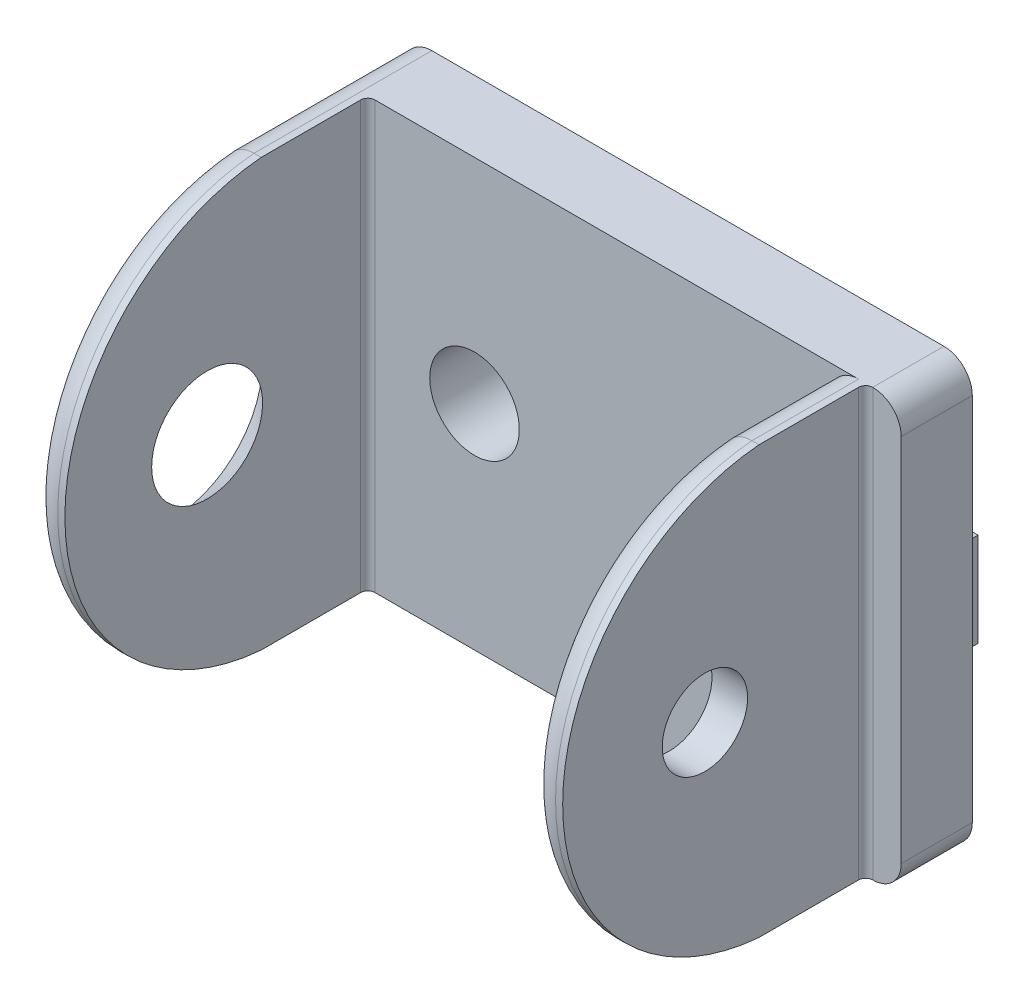
SolidWorks part; units mm, degrees
note: The reader was unsure of these and kept them because the rebuilt part matched: shared geometry of "草图3<3>", "草图3<4>".
ref_plane "前视基准面" through (0, 0, 0) normal (0, 0, 1) x (1, 0, 0)
ref_plane "上视基准面" through (0, 0, 0) normal (0, 1, 0) x (1, 0, 0)
ref_plane "右视基准面" through (0, 0, 0) normal (1, 0, 0) x (0, 0, -1)
other "Configuration Table"
sketch "草图1" plane through (0, 0, 0) normal (0, 0, 1) x (1, 0, 0)
  line L0 (0, 0) -> (40, 0)
  line L1 (40, 0) -> (40, -30)
  line L2 (40, -30) -> (0, -30)
  line L3 (0, -30) -> (0, 0)
  dimension "D1" = 40
  dimension "D2" = 30
extrude "凸台-拉伸1" add sketch "草图1" along normal blind 5
sketch "草图2" plane through (0, 0, 0) normal (0, 0, 1) x (1, 0, 0)
  line L0 (0, 0) -> (2.5, 0)
  line L1 (2.5, 0) -> (2.5, -30)
  line L2 (0, -30) -> (40, -30) construction
  line L3 (2.5, -30) -> (0, -30)
  line L4 (0, -30) -> (0, 0)
  line L5 (0, 0) -> (0, -30)
extrude "凸台-拉伸2" add sketch "草图2" along normal blind 27.5 contours L4 L3 L1 L0
sketch "草图3" plane through (0, 0, 0) normal (0, 0, -1) x (-1, 0, 0)
  line L0 (0, -15) -> (-35.75, -15)
  line L1 (0, 0) -> (0, -30) construction
  line L2 (-40, -30) -> (-40, 0) construction
  line L3 (-35.75, -11.7) -> (-35.75, -18.3)
  line L4 (-35.75, -11.7) -> (-39, -11.7)
  line L5 (-39, -11.7) -> (-39, -18.3)
  line L6 (-39, -18.3) -> (-35.75, -18.3)
  line L7 (-39, -15) -> (-40, -15)
  line L24 (-35.75, -15) -> (-39, -15)
  line L25 (-20, -30) -> (-20, -15)
  line L26 (0, -30) -> (-40, -30) construction
  line L31 (-1, -11.7) -> (-1, -18.3)
  line L32 (-4.25, -11.7) -> (-1, -11.7)
  line L33 (-4.25, -11.7) -> (-4.25, -18.3)
  line L34 (-1, -18.3) -> (-4.25, -18.3)
  line L43 (-33.3, -6) -> (-33.3, -9.25)
  line L44 (-26.7, -9.25) -> (-33.3, -9.25)
  line L45 (-26.7, -9.25) -> (-26.7, -6)
  line L46 (-26.7, -6) -> (-33.3, -6)
  line L63 (-26.7, -24) -> (-26.7, -20.75)
  line L64 (-33.3, -20.75) -> (-26.7, -20.75)
  line L65 (-33.3, -20.75) -> (-33.3, -24)
  line L66 (-33.3, -24) -> (-26.7, -24)
  line L67 (-6.7, -24) -> (-13.3, -24)
  line L68 (-13.3, -24) -> (-13.3, -20.75)
  line L69 (-6.7, -20.75) -> (-13.3, -20.75)
  line L70 (-6.7, -20.75) -> (-6.7, -24)
  line L75 (-13.3, -6) -> (-6.7, -6)
  line L76 (-6.7, -6) -> (-6.7, -9.25)
  line L77 (-13.3, -9.25) -> (-6.7, -9.25)
  line L78 (-13.3, -9.25) -> (-13.3, -6)
  line L79 (-21, -11.7) -> (-24.25, -11.7) [skipped]
  line L80 (-24.25, -18.3) -> (-24.25, -11.7) [skipped]
  line L81 (-24.25, -18.3) -> (-21, -18.3) [skipped]
  line L82 (-21, -18.3) -> (-21, -11.7) [skipped]
  line L83 (-19, -18.3) -> (-19, -11.7) [skipped]
  line L84 (-19, -11.7) -> (-15.75, -11.7) [skipped]
  line L85 (-15.75, -18.3) -> (-15.75, -11.7) [skipped]
  line L86 (-15.75, -18.3) -> (-19, -18.3) [skipped]
  circle A0 centre (-30, -15) radius 3.15
  circle A1 centre (-10, -15) radius 3.15
  point P12 (-35.75, -15)
  point P32 (-35, -10)
  point P37 (-27.5412, -12.4588)
  point P38 (-30, -15)
  point P51 (-10, -15)
  point P58 (-7.5, -12.4792)
  dimension "D1" = 20
  dimension "D2" = 10
  dimension "D3" = 6.3
  dimension "D4" = 6.3
  dimension "D6" = 4
  dimension "D5" = 5.75
  dimension "D7" = 6.6
  dimension "D9" = 3.25
  dimension "D8" = 4
extrude "切除-拉伸1" cut sketch "草图3" against normal blind 3
extrude "切除-拉伸2" cut sketch "草图3<3>" against normal through all contours L0 A0 | L0 A0 | L0 A1 | L0 A1
sketch "草图3<3>" plane through (0, 0, 0) normal (0, 0, -1) x (-1, 0, 0) same geometry as "草图3"
extrude "凸台-拉伸3" add sketch "草图3<4>" along normal blind 1.4 separate body contours L24 L3 L4 L5 | L3 L24 L5 L6 | L32 L33 L0 L31 | L34 L31 L0 L33
sketch "草图3<4>" plane through (0, 0, 0) normal (0, 0, -1) x (-1, 0, 0) same geometry as "草图3"
sketch "草图4" plane through (0, 0, 5) normal (0, 0, 1) x (1, 0, 0)
  line L0 (37.5, 0) -> (35, 0)
  line L1 (40, 0) -> (2.5, 0) construction
  line L2 (35, 0) -> (35, -30)
  line L3 (2.5, -30) -> (40, -30) construction
  line L4 (35, -30) -> (37.5, -30)
  line L5 (37.5, -30) -> (37.5, 0)
  line L6 (40, -30) -> (40, 0) construction
  dimension "D1" = 2.5
  dimension "D2" = 5
extrude "凸台-拉伸4" add sketch "草图4" along normal blind 22.5
sketch "草图5" plane through (0, 0, 0) normal (-1, 0, 0) x (0, 0, 1)
  line L0 (0, 0) -> (0, -30) construction
  line L3 (27.5, 0) -> (0, 0) construction
  line L7 (27.5, -30) -> (0, -30) construction
  line L9 (12.5, 0) -> (27.5, 0)
  line L10 (27.5, 0) -> (27.5, -30)
  line L11 (27.5, -30) -> (10, -30)
  circle A1 centre (16.3, -15) radius 3.15
  arc A2 (12.5, 0) -> (10, -30) centre (11.25, -15) cw
  line M6 (27.5, -30) -> (27.5, 0)
  line M7 (27.5, 0) -> (0, 0)
  dimension "D1" = 16.3
  dimension "D2" = 15
extrude "切除-拉伸3" cut sketch "草图5" against normal through all contours A2 L11 M7 M6
sketch "草图6" plane through (37.5, 0, 0) normal (1, 0, 0) x (0, 0, -1)
  circle A1 centre (-16.302, -15) radius 1.4319
  arc A2 (-12.5, 0) -> (-12.5, -30) centre (-11.25, -15) ccw construction
  point P4 (-26.302, -15)
  dimension "D1" = 10
hole_wizard "M6 螺纹孔1" positions "草图7" profile "草图8" tap size "M6" standard "GB" end condition up to next
sketch "草图7" plane through (37.5, 0, 0) normal (1, 0, 0) x (0, 0, -1)
  point P0 (-16.302, -15)
sketch "草图8" plane through (37.5, -15, 16.302) normal (0, 1, 0) x (0, 0, -1)
  line L0 (0, 0) -> (0, 2.501)
  line L1 (0, 2.501) -> (3, 2.501)
  line L2 (3, 2.501) -> (3, 0)
  line L5 (3, 0) -> (0, 0)
  line L11 (0, -6.35) -> (0, 107.95) construction
  dimension "通孔螺纹孔钻头直径" = 6
  dimension "通孔螺纹孔钻头深度" = 2.501
cosmetic thread "孔螺蚊线1" parameters "D2"=6
hole_wizard "M6 内六角花形半沉头螺钉的锥形沉头孔1" positions "草图11" profile "草图10" countersink size "M6" standard "GB" end condition up to next
sketch "草图11" plane through (0, 0, 0) normal (-1, 0, 0) x (0, 0, 1)
  point P0 (16.3, -15)
sketch "草图10" plane through (0, -15, 16.3) normal (0, 1, 0) x (0, 0, 1)
  line L0 (0, 0) -> (0, 2.501)
  line L1 (0, 2.501) -> (3.3, 2.501)
  line L2 (3.3, 2.501) -> (3.3, 3.1)
  line L3 (3.3, 3.1) -> (6.4, 0)
  line L5 (6.4, 0) -> (0, 0)
  line L6 (-3.3, 3.1) -> (-6.4, 0) construction
  line L11 (0, -6.35) -> (0, 107.95) construction
  dimension "通孔孔直径" = 6.6
  dimension "通孔孔深度" = 2.501
  dimension "近端锥形沉头孔直径" = 12.8
  dimension "近端锥形沉头孔角度" = 90
fillet "圆角3" radius 0.5 2 edges at (37.5, -15, 5) (2.5, -15, 5)
fillet "圆角4" radius 2 4 edges at (40, 0, 2.5) (40, -30, 2.5) (35, -15, 26.302) (0, -15, 26.302)
